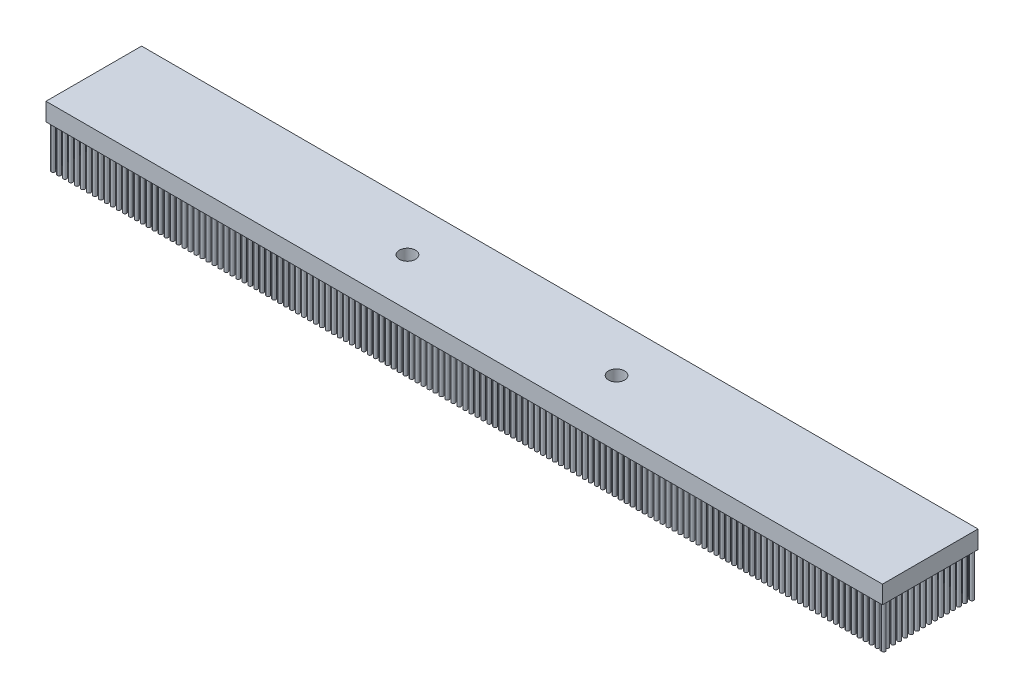
SolidWorks part; units mm, degrees
material "Maple"
ref_plane "Front Plane" through (0, 0, 0) normal (0, 0, 1) x (1, 0, 0)
ref_plane "Top Plane" through (0, 0, 0) normal (0, 1, 0) x (1, 0, 0)
ref_plane "Right Plane" through (0, 0, 0) normal (1, 0, 0) x (0, 0, -1)
sketch "Sketch1" plane through (0, 0, 0) normal (0, 1, 0) x (1, 0, 0)
  line L1 (-350, 40) -> (350, 40)
  line L2 (-350, 40) -> (-350, -40)
  line L3 (-350, -40) -> (350, -40)
  line L4 (350, 40) -> (350, -40)
  line L5 (-350, 40) -> (350, -40) construction
  line L6 (-350, -40) -> (350, 40) construction
  point P0 (0, 0)
  dimension "D1" = 700
  dimension "D2" = 80
extrude "Boss-Extrude1" add sketch "Sketch1" along normal blind 15
sketch "Sketch2" plane through (0, 0, 0) normal (0, 1, 0) x (1, 0, 0)
  line L0 (-8.25, 0) -> (8.25, 0) construction
  line L1 (0, -8.25) -> (0, 8.25) construction
  circle A0 centre (-347, 37) radius 1.5
  circle A1 centre (-342, 37) radius 1.5
  circle A2 centre (-337, 37) radius 1.5
  circle A3 centre (-332, 37) radius 1.5
  circle A4 centre (-327, 37) radius 1.5
  circle A5 centre (-322, 37) radius 1.5
  circle A6 centre (-317, 37) radius 1.5
  circle A7 centre (-312, 37) radius 1.5
  circle A8 centre (-307, 37) radius 1.5
  circle A9 centre (-302, 37) radius 1.5
  circle A10 centre (-297, 37) radius 1.5
  circle A11 centre (-292, 37) radius 1.5
  circle A12 centre (-287, 37) radius 1.5
  circle A13 centre (-282, 37) radius 1.5
  circle A14 centre (-277, 37) radius 1.5
  circle A15 centre (-272, 37) radius 1.5
  circle A16 centre (-267, 37) radius 1.5
  circle A17 centre (-262, 37) radius 1.5
  circle A18 centre (-257, 37) radius 1.5
  circle A19 centre (-252, 37) radius 1.5
  circle A20 centre (-247, 37) radius 1.5
  circle A21 centre (-242, 37) radius 1.5
  circle A22 centre (-237, 37) radius 1.5
  circle A23 centre (-232, 37) radius 1.5
  circle A24 centre (-227, 37) radius 1.5
  circle A25 centre (-222, 37) radius 1.5
  circle A26 centre (-217, 37) radius 1.5
  circle A27 centre (-212, 37) radius 1.5
  circle A28 centre (-207, 37) radius 1.5
  circle A29 centre (-202, 37) radius 1.5
  circle A30 centre (-197, 37) radius 1.5
  circle A31 centre (-192, 37) radius 1.5
  circle A32 centre (-187, 37) radius 1.5
  circle A33 centre (-182, 37) radius 1.5
  circle A34 centre (-177, 37) radius 1.5
  circle A35 centre (-172, 37) radius 1.5
  circle A36 centre (-167, 37) radius 1.5
  circle A37 centre (-162, 37) radius 1.5
  circle A38 centre (-157, 37) radius 1.5
  circle A39 centre (-152, 37) radius 1.5
  circle A40 centre (-147, 37) radius 1.5
  circle A41 centre (-142, 37) radius 1.5
  circle A42 centre (-137, 37) radius 1.5
  circle A43 centre (-132, 37) radius 1.5
  circle A44 centre (-127, 37) radius 1.5
  circle A45 centre (-122, 37) radius 1.5
  circle A46 centre (-117, 37) radius 1.5
  circle A47 centre (-112, 37) radius 1.5
  circle A48 centre (-107, 37) radius 1.5
  circle A49 centre (-102, 37) radius 1.5
  circle A50 centre (-97, 37) radius 1.5
  circle A51 centre (-92, 37) radius 1.5
  circle A52 centre (-87, 37) radius 1.5
  circle A53 centre (-82, 37) radius 1.5
  circle A54 centre (-77, 37) radius 1.5
  circle A55 centre (-72, 37) radius 1.5
  circle A56 centre (-67, 37) radius 1.5
  circle A57 centre (-62, 37) radius 1.5
  circle A58 centre (-57, 37) radius 1.5
  circle A59 centre (-52, 37) radius 1.5
  circle A60 centre (-47, 37) radius 1.5
  circle A61 centre (-42, 37) radius 1.5
  circle A62 centre (-37, 37) radius 1.5
  circle A63 centre (-32, 37) radius 1.5
  circle A64 centre (-27, 37) radius 1.5
  circle A65 centre (-22, 37) radius 1.5
  circle A66 centre (-17, 37) radius 1.5
  circle A67 centre (-12, 37) radius 1.5
  circle A68 centre (-7, 37) radius 1.5
  circle A69 centre (-2, 37) radius 1.5
  circle A70 centre (3, 37) radius 1.5
  circle A71 centre (8, 37) radius 1.5
  circle A72 centre (13, 37) radius 1.5
  circle A73 centre (18, 37) radius 1.5
  circle A74 centre (23, 37) radius 1.5
  circle A75 centre (28, 37) radius 1.5
  circle A76 centre (33, 37) radius 1.5
  circle A77 centre (38, 37) radius 1.5
  circle A78 centre (43, 37) radius 1.5
  circle A79 centre (48, 37) radius 1.5
  circle A80 centre (53, 37) radius 1.5
  circle A81 centre (58, 37) radius 1.5
  circle A82 centre (63, 37) radius 1.5
  circle A83 centre (68, 37) radius 1.5
  circle A84 centre (73, 37) radius 1.5
  circle A85 centre (78, 37) radius 1.5
  circle A86 centre (83, 37) radius 1.5
  circle A87 centre (88, 37) radius 1.5
  circle A88 centre (93, 37) radius 1.5
  circle A89 centre (98, 37) radius 1.5
  circle A90 centre (103, 37) radius 1.5
  circle A91 centre (108, 37) radius 1.5
  circle A92 centre (113, 37) radius 1.5
  circle A93 centre (118, 37) radius 1.5
  circle A94 centre (123, 37) radius 1.5
  circle A95 centre (128, 37) radius 1.5
  circle A96 centre (133, 37) radius 1.5
  circle A97 centre (138, 37) radius 1.5
  circle A98 centre (143, 37) radius 1.5
  circle A99 centre (148, 37) radius 1.5
  circle A100 centre (153, 37) radius 1.5
  circle A101 centre (158, 37) radius 1.5
  circle A102 centre (163, 37) radius 1.5
  circle A103 centre (168, 37) radius 1.5
  circle A104 centre (173, 37) radius 1.5
  circle A105 centre (178, 37) radius 1.5
  circle A106 centre (183, 37) radius 1.5
  circle A107 centre (188, 37) radius 1.5
  circle A108 centre (193, 37) radius 1.5
  circle A109 centre (198, 37) radius 1.5
  circle A110 centre (203, 37) radius 1.5
  circle A111 centre (208, 37) radius 1.5
  circle A112 centre (213, 37) radius 1.5
  circle A113 centre (218, 37) radius 1.5
  circle A114 centre (223, 37) radius 1.5
  circle A115 centre (228, 37) radius 1.5
  circle A116 centre (233, 37) radius 1.5
  circle A117 centre (238, 37) radius 1.5
  circle A118 centre (243, 37) radius 1.5
  circle A119 centre (248, 37) radius 1.5
  circle A120 centre (253, 37) radius 1.5
  circle A121 centre (258, 37) radius 1.5
  circle A122 centre (263, 37) radius 1.5
  circle A123 centre (268, 37) radius 1.5
  circle A124 centre (273, 37) radius 1.5
  circle A125 centre (278, 37) radius 1.5
  circle A126 centre (283, 37) radius 1.5
  circle A127 centre (288, 37) radius 1.5
  circle A128 centre (293, 37) radius 1.5
  circle A129 centre (298, 37) radius 1.5
  circle A130 centre (303, 37) radius 1.5
  circle A131 centre (308, 37) radius 1.5
  circle A132 centre (313, 37) radius 1.5
  circle A133 centre (318, 37) radius 1.5
  circle A134 centre (323, 37) radius 1.5
  circle A135 centre (328, 37) radius 1.5
  circle A136 centre (333, 37) radius 1.5
  circle A137 centre (338, 37) radius 1.5
  circle A138 centre (343, 37) radius 1.5
  circle A139 centre (348, 37) radius 1.5
  circle A140 centre (-347, 32) radius 1.5
  circle A141 centre (-347, 27) radius 1.5
  circle A142 centre (-347, 22) radius 1.5
  circle A143 centre (-347, 17) radius 1.5
  circle A144 centre (-347, 12) radius 1.5
  circle A145 centre (-347, 7) radius 1.5
  circle A146 centre (-347, 2) radius 1.5
  circle A147 centre (-347, -3) radius 1.5
  circle A148 centre (-347, -8) radius 1.5
  circle A149 centre (-347, -13) radius 1.5
  circle A150 centre (-347, -18) radius 1.5
  circle A151 centre (-347, -23) radius 1.5
  circle A152 centre (-347, -28) radius 1.5
  circle A153 centre (-347, -33) radius 1.5
  circle A154 centre (348, -37) radius 1.5
  circle A155 centre (343, -37) radius 1.5
  circle A156 centre (338, -37) radius 1.5
  circle A157 centre (333, -37) radius 1.5
  circle A158 centre (328, -37) radius 1.5
  circle A159 centre (323, -37) radius 1.5
  circle A160 centre (318, -37) radius 1.5
  circle A161 centre (313, -37) radius 1.5
  circle A162 centre (308, -37) radius 1.5
  circle A163 centre (303, -37) radius 1.5
  circle A164 centre (298, -37) radius 1.5
  circle A165 centre (293, -37) radius 1.5
  circle A166 centre (288, -37) radius 1.5
  circle A167 centre (283, -37) radius 1.5
  circle A168 centre (278, -37) radius 1.5
  circle A169 centre (273, -37) radius 1.5
  circle A170 centre (268, -37) radius 1.5
  circle A171 centre (263, -37) radius 1.5
  circle A172 centre (258, -37) radius 1.5
  circle A173 centre (253, -37) radius 1.5
  circle A174 centre (248, -37) radius 1.5
  circle A175 centre (243, -37) radius 1.5
  circle A176 centre (238, -37) radius 1.5
  circle A177 centre (233, -37) radius 1.5
  circle A178 centre (228, -37) radius 1.5
  circle A179 centre (223, -37) radius 1.5
  circle A180 centre (218, -37) radius 1.5
  circle A181 centre (213, -37) radius 1.5
  circle A182 centre (208, -37) radius 1.5
  circle A183 centre (203, -37) radius 1.5
  circle A184 centre (198, -37) radius 1.5
  circle A185 centre (193, -37) radius 1.5
  circle A186 centre (188, -37) radius 1.5
  circle A187 centre (183, -37) radius 1.5
  circle A188 centre (178, -37) radius 1.5
  circle A189 centre (173, -37) radius 1.5
  circle A190 centre (168, -37) radius 1.5
  circle A191 centre (163, -37) radius 1.5
  circle A192 centre (158, -37) radius 1.5
  circle A193 centre (153, -37) radius 1.5
  circle A194 centre (148, -37) radius 1.5
  circle A195 centre (143, -37) radius 1.5
  circle A196 centre (138, -37) radius 1.5
  circle A197 centre (133, -37) radius 1.5
  circle A198 centre (128, -37) radius 1.5
  circle A199 centre (123, -37) radius 1.5
  circle A200 centre (118, -37) radius 1.5
  circle A201 centre (113, -37) radius 1.5
  circle A202 centre (108, -37) radius 1.5
  circle A203 centre (103, -37) radius 1.5
  circle A204 centre (98, -37) radius 1.5
  circle A205 centre (93, -37) radius 1.5
  circle A206 centre (88, -37) radius 1.5
  circle A207 centre (83, -37) radius 1.5
  circle A208 centre (78, -37) radius 1.5
  circle A209 centre (73, -37) radius 1.5
  circle A210 centre (68, -37) radius 1.5
  circle A211 centre (63, -37) radius 1.5
  circle A212 centre (58, -37) radius 1.5
  circle A213 centre (53, -37) radius 1.5
  circle A214 centre (48, -37) radius 1.5
  circle A215 centre (43, -37) radius 1.5
  circle A216 centre (38, -37) radius 1.5
  circle A217 centre (33, -37) radius 1.5
  circle A218 centre (28, -37) radius 1.5
  circle A219 centre (23, -37) radius 1.5
  circle A220 centre (18, -37) radius 1.5
  circle A221 centre (13, -37) radius 1.5
  circle A222 centre (8, -37) radius 1.5
  circle A223 centre (3, -37) radius 1.5
  circle A224 centre (-2, -37) radius 1.5
  circle A225 centre (-7, -37) radius 1.5
  circle A226 centre (-12, -37) radius 1.5
  circle A227 centre (-17, -37) radius 1.5
  circle A228 centre (-22, -37) radius 1.5
  circle A229 centre (-27, -37) radius 1.5
  circle A230 centre (-32, -37) radius 1.5
  circle A231 centre (-37, -37) radius 1.5
  circle A232 centre (-42, -37) radius 1.5
  circle A233 centre (-47, -37) radius 1.5
  circle A234 centre (-52, -37) radius 1.5
  circle A235 centre (-57, -37) radius 1.5
  circle A236 centre (-62, -37) radius 1.5
  circle A237 centre (-67, -37) radius 1.5
  circle A238 centre (-72, -37) radius 1.5
  circle A239 centre (-77, -37) radius 1.5
  circle A240 centre (-82, -37) radius 1.5
  circle A241 centre (-87, -37) radius 1.5
  circle A242 centre (-92, -37) radius 1.5
  circle A243 centre (-97, -37) radius 1.5
  circle A244 centre (-102, -37) radius 1.5
  circle A245 centre (-107, -37) radius 1.5
  circle A246 centre (-112, -37) radius 1.5
  circle A247 centre (-117, -37) radius 1.5
  circle A248 centre (-122, -37) radius 1.5
  circle A249 centre (-127, -37) radius 1.5
  circle A250 centre (-132, -37) radius 1.5
  circle A251 centre (-137, -37) radius 1.5
  circle A252 centre (-142, -37) radius 1.5
  circle A253 centre (-147, -37) radius 1.5
  circle A254 centre (-152, -37) radius 1.5
  circle A255 centre (-157, -37) radius 1.5
  circle A256 centre (-162, -37) radius 1.5
  circle A257 centre (-167, -37) radius 1.5
  circle A258 centre (-172, -37) radius 1.5
  circle A259 centre (-177, -37) radius 1.5
  circle A260 centre (-182, -37) radius 1.5
  circle A261 centre (-187, -37) radius 1.5
  circle A262 centre (-192, -37) radius 1.5
  circle A263 centre (-197, -37) radius 1.5
  circle A264 centre (-202, -37) radius 1.5
  circle A265 centre (-207, -37) radius 1.5
  circle A266 centre (-212, -37) radius 1.5
  circle A267 centre (-217, -37) radius 1.5
  circle A268 centre (-222, -37) radius 1.5
  circle A269 centre (-227, -37) radius 1.5
  circle A270 centre (-232, -37) radius 1.5
  circle A271 centre (-237, -37) radius 1.5
  circle A272 centre (-242, -37) radius 1.5
  circle A273 centre (-247, -37) radius 1.5
  circle A274 centre (-252, -37) radius 1.5
  circle A275 centre (-257, -37) radius 1.5
  circle A276 centre (-262, -37) radius 1.5
  circle A277 centre (-267, -37) radius 1.5
  circle A278 centre (-272, -37) radius 1.5
  circle A279 centre (-277, -37) radius 1.5
  circle A280 centre (-282, -37) radius 1.5
  circle A281 centre (-287, -37) radius 1.5
  circle A282 centre (-292, -37) radius 1.5
  circle A283 centre (-297, -37) radius 1.5
  circle A284 centre (-302, -37) radius 1.5
  circle A285 centre (-307, -37) radius 1.5
  circle A286 centre (-312, -37) radius 1.5
  circle A287 centre (-317, -37) radius 1.5
  circle A288 centre (-322, -37) radius 1.5
  circle A289 centre (-327, -37) radius 1.5
  circle A290 centre (-332, -37) radius 1.5
  circle A291 centre (-337, -37) radius 1.5
  circle A292 centre (-342, -37) radius 1.5
  circle A293 centre (-347, -37) radius 1.5
  circle A294 centre (347, -37) radius 1.5
  circle A295 centre (347, -33) radius 1.5
  circle A296 centre (347, -28) radius 1.5
  circle A297 centre (347, -23) radius 1.5
  circle A298 centre (347, -18) radius 1.5
  circle A299 centre (347, -13) radius 1.5
  circle A300 centre (347, -8) radius 1.5
  circle A301 centre (347, -3) radius 1.5
  circle A302 centre (347, 2) radius 1.5
  circle A303 centre (347, 7) radius 1.5
  circle A304 centre (347, 12) radius 1.5
  circle A305 centre (347, 17) radius 1.5
  circle A306 centre (347, 22) radius 1.5
  circle A307 centre (347, 27) radius 1.5
  circle A308 centre (347, 32) radius 1.5
  circle A309 centre (347, 37) radius 1.5
  dimension "D1" = 3
  dimension "D2" = 347
  dimension "D3" = 37
  dimension "D4" = 140
  dimension "D5" = 15
extrude "Boss-Extrude2" add sketch "Sketch2" against normal blind 35.58
sketch "Sketch3" plane through (0, 0, 0) normal (0, 1, 0) x (1, 0, 0)
  line L0 (-87.5, 0) -> (87.5, 0) construction
  circle A0 centre (-87.5, 0) radius 6.725
  circle A1 centre (87.5, 0) radius 6.725
  point P4 (0, 0)
  dimension "D2" = 13.45
  dimension "D1" = 175
extrude "Cut-Extrude1" cut sketch "Sketch3" against normal through all both and the other way through all
equation "\"broomLength\"= 700mm"
equation "\"broomWidth\"= 80mm"
equation "\"D1@Sketch1\"=\"broomLength\""
equation "\"D2@Sketch1\"=\"broomWidth\""
equation "\"D2@Sketch2\"=\"broomLength\"/2 -3"
equation "\"D3@Sketch2\"=\"broomWidth\"/2 - 3"
equation "\"mountHoleDiameter\"= 1in / 2 + 0.75"
equation "\"D2@Sketch3\"=\"mountHoleDiameter\""
